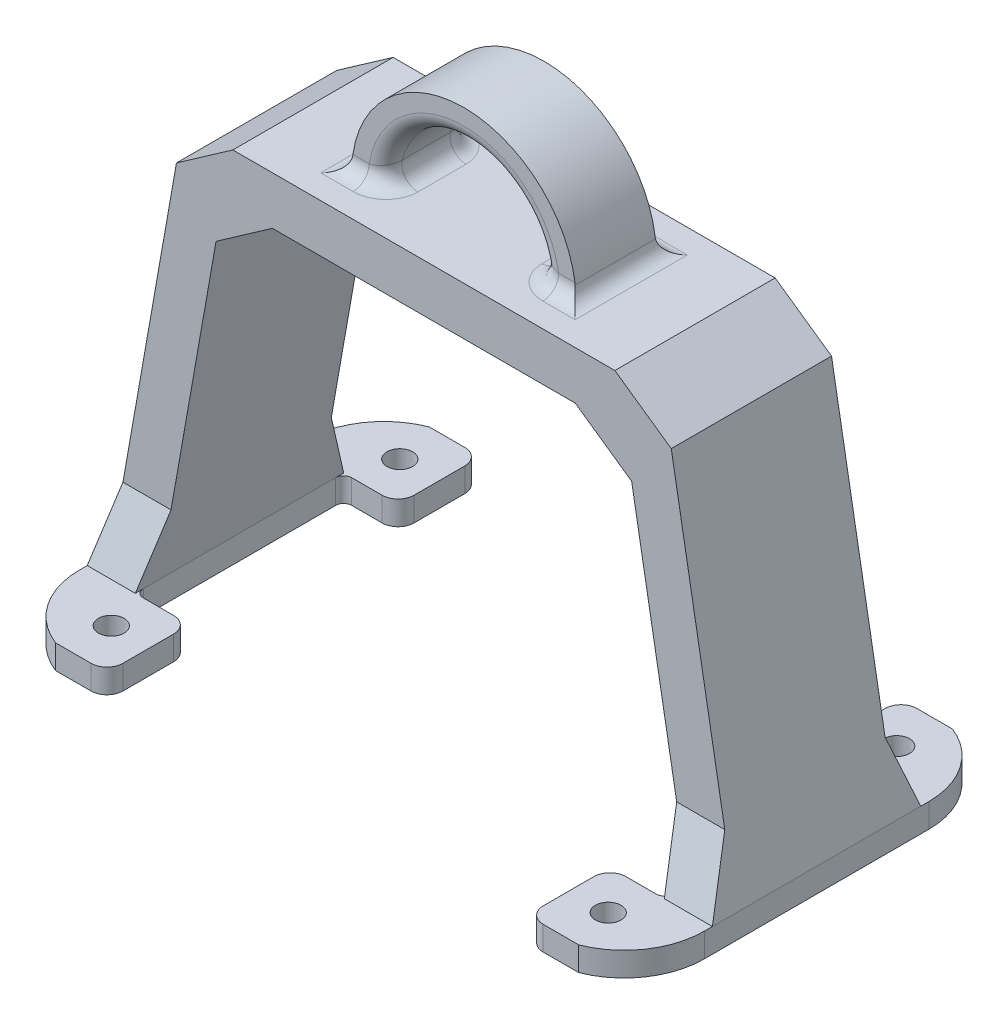
SolidWorks part; units mm, degrees
ref_plane "Front" through (0, 0, 0) normal (0, 0, 1) x (1, 0, 0)
ref_plane "Top" through (0, 0, 0) normal (0, 1, 0) x (1, 0, 0)
ref_plane "Right" through (0, 0, 0) normal (1, 0, 0) x (0, 0, -1)
sketch "Sketch1" plane through (0, 0, 0) normal (0, 1, 0) x (1, 0, 0)
  line L0 (4.7848, 3.3707) -> (4.7848, 39.3707) construction
  line L5 (6.4212, -1.9508) -> (0, -1.9508)
  line L6 (0, -1.9508) -> (0, 8.3707)
  line L7 (0, 8.3707) -> (6.7848, 8.3707)
  line L8 (6.7848, 8.3707) -> (6.7848, 34.3707)
  line L9 (6.7848, 34.3707) -> (0, 34.3707)
  line L10 (0, 34.3707) -> (0, 44.6922)
  line L11 (0, 44.6922) -> (6.4212, 44.6922)
  line L12 (12.7848, 35.3768) -> (12.7848, 7.3646)
  circle A0 centre (4.7848, 3.3707) radius 1.6
  circle A1 centre (4.7848, 39.3707) radius 1.6
  arc A2 (6.4212, 44.6922) -> (12.7848, 35.3768) centre (2.7848, 35.3768) cw
  arc A3 (12.7848, 7.3646) -> (6.4212, -1.9508) centre (2.7848, 7.3646) cw
  point P5 (4.7848, 3.3707)
  dimension "D3" = 3.2
  dimension "D1" = 3.2
  dimension "D9" = 10
  dimension "D2" = 36
  dimension "D4" = 10.3215
  dimension "D5" = 1.9508
  dimension "D6" = 26
  dimension "D7" = 28.0122
  dimension "D8" = 6.4212
  dimension "D10" = 6.7848
  dimension "D11" = 6
  dimension "D12" = 4.7848
  dimension "D13" = 5
extrude "Boss-Extrude1" add sketch "Sketch1" along normal blind 3
ref_plane "Plane1" through (0, 0, -21.3707) normal (0, 0, 1) x (1, 0, 0)
sketch "Sketch2" plane through (0, 0, -21.3707) normal (0, 0, 1) x (1, 0, 0)
  line L0 (12.7848, 3) -> (4.8415, 48)
  line L1 (12.7848, 3) -> (6.4212, 3) construction
  line L2 (6.7848, 3) -> (-1.1585, 48)
  line L3 (6.7848, 3) -> (12.7848, 3)
  line L4 (-26.2177, 0) -> (-26.2177, 48) construction
  line L5 (-26.2177, 48) -> (-1.1585, 48)
  line L6 (-26.2177, 54) -> (3.7823, 54)
  line L7 (3.7823, 54) -> (4.8415, 48)
  line L8 (-26.2177, 54) -> (-26.2177, 48)
  dimension "D1" = 6
  dimension "D2" = 45
  dimension "D3" = 6
  dimension "D4" = 26.2177
  dimension "D5" = 30
extrude "Boss-Extrude2" add sketch "Sketch2" along normal blind 10 and the other way blind 10
chamfer "Chamfer1" distance 3 angle 70 2 edges at (9.7848, 3, -11.3707) (9.7848, 3, -31.3707)
chamfer "Chamfer2" distance 5 angle 45 2 edges at (-1.1585, 48, -21.3707) (3.7823, 54, -21.3707)
mirror "Mirror1" about plane through (-26.2177, 54, -31.3707) normal (-1, 0, 0) of bodies 102
fillet "Fillet1" radius 1 4 edges at (-59.2201, 1.5, -34.3707) (-59.2201, 1.5, -8.3707) (6.7848, 1.5, -34.3707) (6.7848, 1.5, -8.3707)
fillet "Fillet2" radius 2 8 edges at (-52.4353, 1.5, -8.3707) (-52.4353, 1.5, 1.9508) (-52.4353, 1.5, -34.3707) (-52.4353, 1.5, -44.6922) (0, 1.5, -8.3707) (0, 1.5, 1.9508) (0, 1.5, -34.3707) (0, 1.5, -44.6922)
ref_plane "Plane2" through (0, 0, -21.3707) normal (0, 0, 1) x (1, 0, 0)
sketch "Sketch3" plane through (0, 0, -21.3707) normal (0, 0, 1) x (1, 0, 0)
  line L0 (-26.2177, 54) -> (-26.2177, 64) construction
  line L1 (-2.3833, 54) -> (-50.052, 54) construction
  line L2 (-40.2177, 54) -> (-36.2177, 54)
  line L3 (-16.2177, 54) -> (-12.2177, 54)
  arc A0 (-36.2177, 54) -> (-16.2177, 54) centre (-26.2177, 54) cw
  arc A1 (-40.2177, 54) -> (-12.2177, 54) centre (-26.2177, 54) cw
  point P7 (-26.2177, 64)
  dimension "D1" = 10
  dimension "D3" = 4
extrude "Boss-Extrude3" add sketch "Sketch3" along normal blind 5 and the other way blind 5
fillet "Fillet3" radius 2 10 edges at (-14.2177, 54, -26.3707) (-38.2177, 54, -26.3707) (-14.2177, 54, -16.3707) (-38.2177, 54, -16.3707) (-12.2177, 54, -21.3707) (-40.2177, 54, -21.3707) (-16.2177, 54, -21.3707) (-36.2177, 54, -21.3707) (-26.2177, 64, -26.3707) (-26.2177, 64, -16.3707)
